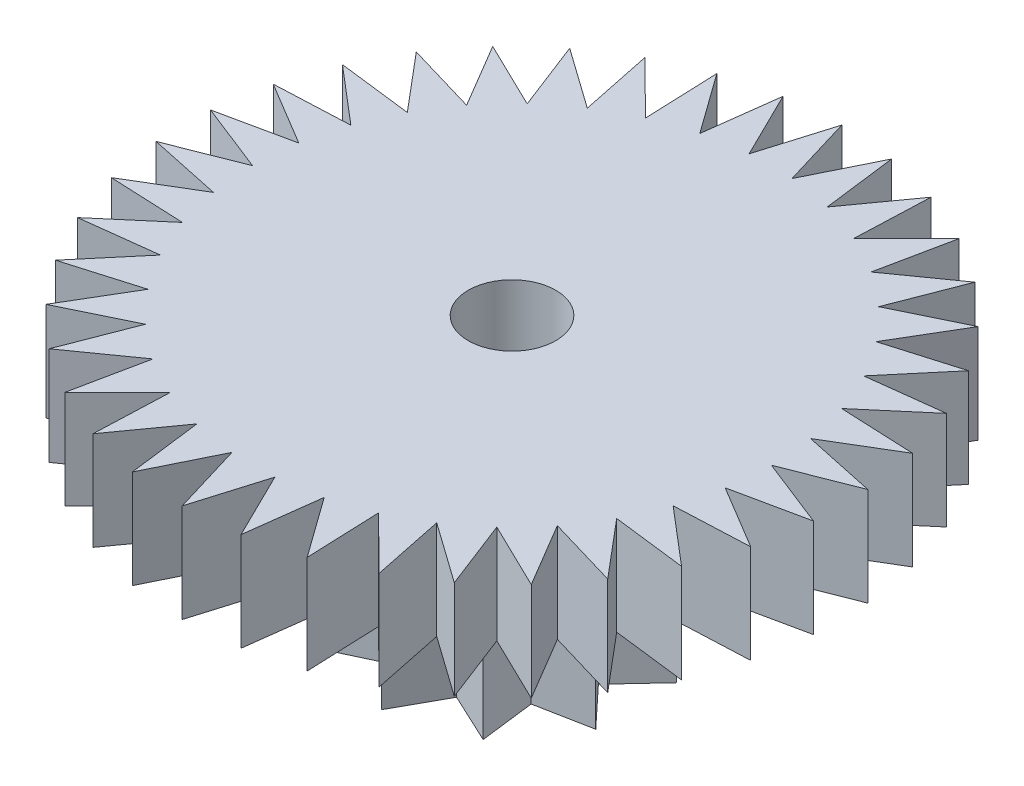
SolidWorks part; units mm, degrees
ref_plane "Front Plane" through (0, 0, 0) normal (0, 0, 1) x (1, 0, 0)
ref_plane "Top Plane" through (0, 0, 0) normal (0, 1, 0) x (1, 0, 0)
ref_plane "Right Plane" through (0, 0, 0) normal (1, 0, 0) x (0, 0, -1)
sketch "Sketch1" plane through (0, 0, 0) normal (0, 0, 1) x (1, 0, 0)
  line L0 (-6.03, 5.05) -> (-6.03, 3.25)
  line L1 (-6.03, 3.25) -> (-2.385, 3.25)
  line L2 (-2.385, 3.25) -> (-2.385, 0)
  line L3 (-2.385, 0) -> (0, 0)
  line L4 (-6.03, 5.05) -> (0, 5.05)
  line L5 (0, 5.05) -> (0, 0) construction
  line L6 (0, 0) -> (0, 5.05)
  dimension "D1" = 6.03
  dimension "D2" = 1.8
  dimension "D3" = 5.05
  dimension "D4" = 2.385
revolve "Revolve1" add sketch "Sketch1" angle 360 about L5
sketch "Sketch2" plane through (0, 5.05, 0) normal (0, 1, 0) x (1, 0, 0)
  circle A0 centre (0, 0) radius 0.8
  dimension "D1" = 1.6
extrude "Cut-Extrude1" cut sketch "Sketch2" against normal through all
sketch "Sketch6" [suppressed] plane through (0, 5.05, 0) normal (0, 1, 0) x (-1, 0, 0)
  circle A0 centre (0, 0) radius 1
  dimension "D1" = 2
extrude "Cut-Extrude4" [suppressed] cut sketch "Sketch6" against normal through all
ref_axis "Axis1" through (0, -0.2525, 0) along (0, 1, 0)
sketch "Sketch3" plane through (0, 5.05, 0) normal (0, 1, 0) x (1, 0, 0)
  line L0 (0, 0) -> (0, 6.03) construction
  line L1 (0, 0) -> (0.9925, 5.9478) construction
  line L2 (0, 0) -> (0.498, 6.0094) construction
  line L3 (0, 6.03) -> (0.3917, 4.727)
  line L4 (0.3917, 4.727) -> (0.9925, 5.9478)
  circle A0 centre (0, 0) radius 4.7432 construction
  circle A1 centre (0, 0) radius 6.03 construction
  arc A2 (0, 6.03) -> (0.9925, 5.9478) centre (0, 0) cw
  dimension "D1" = 9.474
extrude "Cut-Extrude2" cut sketch "Sketch3" against normal through all
pattern_circular "CirPattern1" count 38 over 360 about axis through (0, -0.2525, 0) along (0, 1, 0) of "Cut-Extrude2"
sketch "Sketch4" plane through (0, 0, 0) normal (0, -1, 0) x (1, 0, 0)
  line L0 (0, 0) -> (0, 2.385) construction
  line L1 (0, 0) -> (1.4019, 1.9295) construction
  line L2 (0, 0) -> (0.737, 2.2683) construction
  line L3 (1.4019, 1.9295) -> (0.488, 1.502)
  line L4 (0.488, 1.502) -> (0, 2.385)
  circle A0 centre (0, 0) radius 2.385 construction
  arc A1 (0, 2.385) -> (1.4019, 1.9295) centre (0, 0) cw
  circle A2 centre (0, 0) radius 1.5793 construction
  dimension "D1" = 36
extrude "Cut-Extrude3" cut sketch "Sketch4" against normal up to surface (3.25 mm away) up to face at (0, 3.25, 0)
pattern_circular "CirPattern2" count 10 over 360 about axis through (0, -0.2525, 0) along (0, 1, 0) of "Cut-Extrude3"
sketch "Sketch for Gear Mate" plane through (0, 5.05, 0) normal (0, 1, 0) x (1, 0, 0)
  circle A0 centre (0, 0) radius 2.1595
